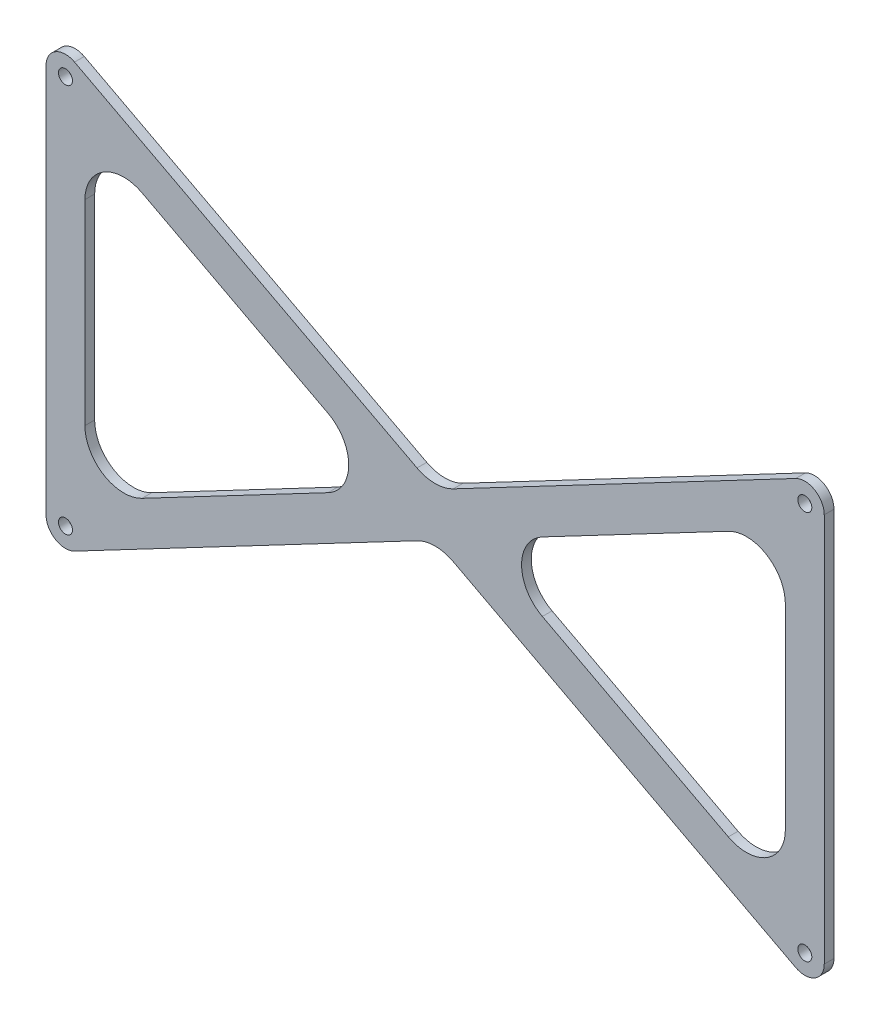
SolidWorks part; units mm, degrees
ref_plane "Front Plane" through (0, 0, 0) normal (0, 0, 1) x (1, 0, 0)
ref_plane "Top Plane" through (0, 0, 0) normal (0, 1, 0) x (1, 0, 0)
ref_plane "Right Plane" through (0, 0, 0) normal (1, 0, 0) x (0, 0, -1)
sketch "Sketch1" plane through (0, 0, 0) normal (0, 0, 1) x (1, 0, 0)
  line L0 (-120.65, -63.5) -> (120.65, 63.5) construction
  line L3 (-114.3, -52.9821) -> (-13.634, 0)
  line L10 (-117.6925, -69.1192) -> (0, -7.1758)
  line L11 (-120.65, 63.5) -> (120.65, -63.5) construction
  line L12 (-117.6925, 69.1192) -> (0, 7.1758)
  line L13 (-114.3, 52.9821) -> (-13.634, 0)
  line L14 (0, 7.1758) -> (117.6925, 69.1192)
  line L15 (0, -7.1758) -> (117.6925, -69.1192)
  line L16 (13.634, 0) -> (114.3, 52.9821)
  line L17 (13.634, 0) -> (114.3, -52.9821)
  line L18 (-127, 63.5) -> (-127, -63.5)
  line L19 (-114.3, 52.9821) -> (-114.3, -52.9821)
  line L20 (127, 63.5) -> (127, -63.5)
  line L21 (114.3, 52.9821) -> (114.3, -52.9821)
  arc A4 (-127, -63.5) -> (-117.6925, -69.1192) centre (-120.65, -63.5) ccw
  arc A5 (127, 63.5) -> (117.6925, 69.1192) centre (120.65, 63.5) ccw
  arc A6 (-117.6925, 69.1192) -> (-127, 63.5) centre (-120.65, 63.5) ccw
  arc A7 (117.6925, -69.1192) -> (127, -63.5) centre (120.65, -63.5) ccw
  point P2 (0, 0)
  point P9 (0, 0)
  point P13 (0, 0)
  point P26 (0, 0)
  dimension "D1" = 254
  dimension "D3" = 6.35
  dimension "D2" = 127
extrude "Boss-Extrude1" add sketch "Sketch1" along normal blind 3.175
sketch "Sketch2" plane through (0, 0, 3.175) normal (0, 0, 1) x (1, 0, 0)
  circle A0 centre (-120.65, 63.5) radius 2.286
  circle A1 centre (-120.65, -63.5) radius 2.286
  circle A2 centre (120.65, -63.5) radius 2.286
  circle A3 centre (120.65, 63.5) radius 2.286
  arc A4 (-117.6925, 69.1192) -> (-127, 63.5) centre (-120.65, 63.5) ccw construction
  arc A5 (-127, -63.5) -> (-117.6925, -69.1192) centre (-120.65, -63.5) ccw construction
  arc A6 (117.6925, -69.1192) -> (127, -63.5) centre (120.65, -63.5) ccw construction
  arc A7 (127, 63.5) -> (117.6925, 69.1192) centre (120.65, 63.5) ccw construction
  dimension "D1" = 4.572
extrude "Cut-Extrude1" cut sketch "Sketch2" against normal through all
fillet "Fillet1" radius 12.7 8 edges at (114.3, -52.9821, 1.5875) (114.3, 52.9821, 1.5875) (13.634, 0, 1.5875) (-114.3, -52.9821, 1.5875) (-13.634, 0, 1.5875) (-114.3, 52.9821, 1.5875) (0, 7.1758, 1.5875) (0, -7.1758, 1.5875)
